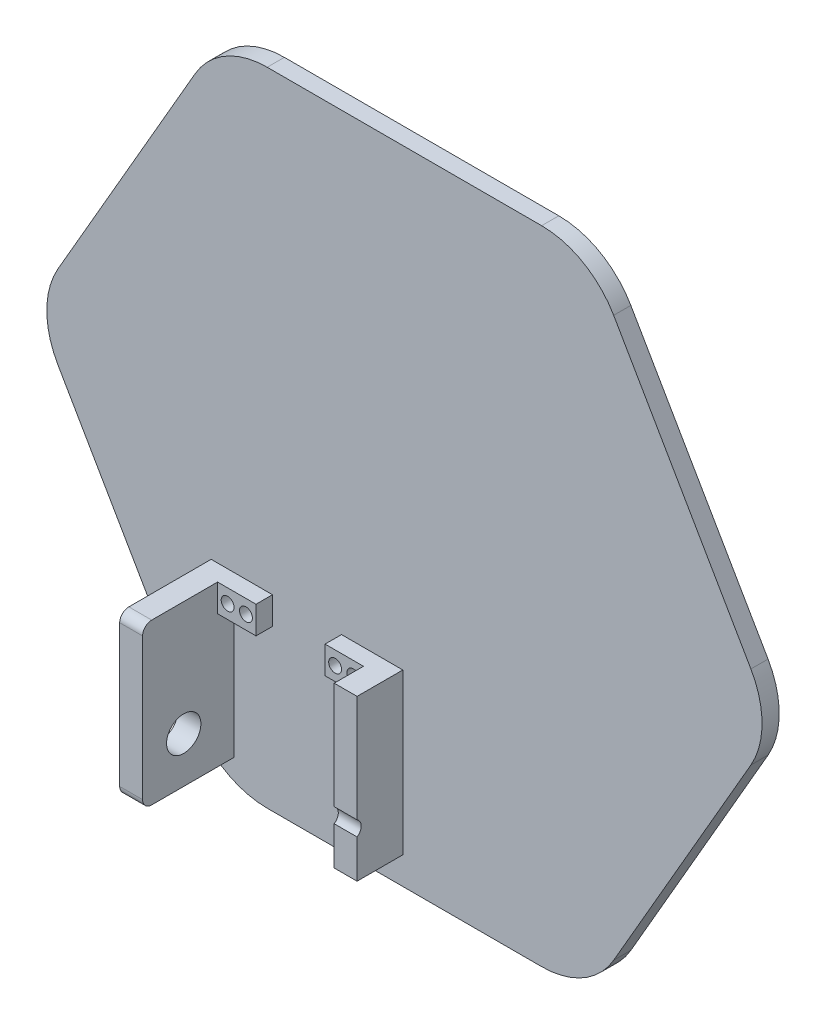
SolidWorks part; units mm, degrees
ref_plane "Front Plane" through (0, 0, 0) normal (0, 0, 1) x (1, 0, 0)
ref_plane "Top Plane" through (0, 0, 0) normal (0, 1, 0) x (1, 0, 0)
ref_plane "Right Plane" through (0, 0, 0) normal (1, 0, 0) x (0, 0, -1)
sketch "Sketch2" plane through (0, 0, 0) normal (0, 0, 1) x (1, 0, 0)
  line L1 (96.2019, 11.5481) -> (58.1019, 77.5392)
  line L2 (38.1, 89.0873) -> (-38.1, 89.0873)
  line L3 (-58.1019, 77.5392) -> (-96.2019, 11.5481)
  line L4 (-96.2019, -11.5481) -> (-58.1019, -77.5392)
  line L5 (-38.1, -89.0873) -> (38.1, -89.0873)
  line L6 (58.1019, -77.5392) -> (96.2019, -11.5481)
  circle A0 centre (0, 0) radius 89.0873 construction
  arc A1 (58.1019, 77.5392) -> (38.1, 89.0873) centre (38.1, 65.9911) ccw
  arc A2 (96.2019, 11.5481) -> (96.2019, -11.5481) centre (76.2, 0) cw
  arc A3 (38.1, -89.0873) -> (58.1019, -77.5392) centre (38.1, -65.9911) ccw
  arc A4 (-58.1019, -77.5392) -> (-38.1, -89.0873) centre (-38.1, -65.9911) ccw
  arc A5 (-96.2019, 11.5481) -> (-96.2019, -11.5481) centre (-76.2, 0) ccw
  arc A6 (-38.1, 89.0873) -> (-58.1019, 77.5392) centre (-38.1, 65.9911) ccw
  dimension "D1" = 76.2
extrude "Boss-Extrude1" add sketch "Sketch2" along normal blind 4.7625
sketch "Sketch4" plane through (0, 0, 4.7625) normal (0, 0, 1) x (1, 0, 0)
  line L0 (-38.1, -89.0873) -> (38.1, -89.0873) construction
  line L1 (-53.6569, -81.4673) -> (-47.3069, -81.4673)
  line L2 (-53.6569, -81.4673) -> (-53.6569, -37.0173)
  line L3 (-53.6569, -37.0173) -> (-47.3069, -37.0173)
  line L4 (-47.3069, -81.4673) -> (-47.3069, -37.0173)
  point P17 (0, 0)
  dimension "D1" = 6.35
  dimension "D2" = 44.45
  dimension "D3" = 7.62
  dimension "D4" = 4.445
extrude "Boss-Extrude3" add sketch "Sketch4" along normal blind 25.4
sketch "Sketch5" plane through (0, 0, 4.7625) normal (0, 0, 1) x (1, 0, 0)
  line L1 (-6.7975, -81.4673) -> (-0.4475, -81.4673)
  line L2 (-6.7975, -81.4673) -> (-6.7975, -37.0173)
  line L3 (-6.7975, -37.0173) -> (-0.4475, -37.0173)
  line L4 (-0.4475, -81.4673) -> (-0.4475, -37.0173)
  line L6 (-53.6569, -81.4673) -> (-47.3069, -81.4673) construction
  point P19 (0, 0)
  dimension "D1" = 6.35
extrude "Boss-Extrude6" add sketch "Sketch5" along normal blind 12.7
sketch "Sketch6" plane through (0, 0, 4.7625) normal (0, 0, 1) x (1, 0, 0)
  line L0 (-17.4655, -37.0173) -> (-6.7975, -37.0173)
  line L1 (-47.3069, -37.0173) -> (-36.6389, -37.0173)
  line L2 (-47.3069, -37.0173) -> (-47.3069, -44.6373)
  line L3 (-47.3069, -44.6373) -> (-36.6389, -44.6373)
  line L4 (-36.6389, -37.0173) -> (-36.6389, -44.6373)
  line L5 (-17.4655, -37.0173) -> (-17.4655, -44.6373)
  line L6 (-17.4655, -44.6373) -> (-6.7975, -44.6373)
  line L7 (-6.7975, -37.0173) -> (-6.7975, -44.6373)
  line L8 (-6.7975, -37.0173) -> (-6.7975, -81.4673) construction
  line L9 (-0.4475, -37.0173) -> (-6.7975, -37.0173) construction
  line L10 (-0.4475, -81.4673) -> (-0.4475, -37.0173) construction
  line L12 (-53.6569, -37.0173) -> (-53.6569, -81.4673) construction
  point P16 (0, 0)
  dimension "D1" = 7.62
  dimension "D2" = 17.018
  dimension "D3" = 7.62
  dimension "D4" = 17.018
extrude "Boss-Extrude5" add sketch "Sketch6" along normal blind 4.572
sketch "Sketch7" plane through (0, 0, 9.3345) normal (0, 0, 1) x (1, 0, 0)
  line L0 (-47.3069, -44.6373) -> (-36.6389, -44.6373) construction
  line L1 (-36.6389, -44.6373) -> (-36.6389, -37.0173) construction
  line L2 (-17.4655, -44.6373) -> (-6.7975, -44.6373) construction
  line L3 (-17.4655, -37.0173) -> (-17.4655, -44.6373) construction
  circle A0 centre (-44.5129, -40.8273) radius 1.7907
  circle A1 centre (-39.4329, -40.8273) radius 1.7907
  circle A2 centre (-14.6715, -40.8273) radius 1.7907
  circle A3 centre (-9.5915, -40.8273) radius 1.7907
  dimension "D1" = 3.5814
  dimension "D2" = 3.81
  dimension "D8" = 3.5814
  dimension "D9" = 3.5814
  dimension "D10" = 3.5814
  dimension "D3" = 5.08
  dimension "D4" = 2.794
  dimension "D5" = 3.81
  dimension "D6" = 2.794
  dimension "D7" = 5.08
extrude "Cut-Extrude1" cut sketch "Sketch7" against normal blind 6.731
sketch "Sketch9" plane through (-53.6569, 0, 0) normal (-1, 0, 0) x (0, 0, 1)
  line L0 (4.7625, -37.0173) -> (4.7625, -81.4673) construction
  line L1 (30.1625, -81.4673) -> (4.7625, -81.4673) construction
  circle A0 centre (7.5311, -68.7673) radius 2.286
  dimension "D1" = 4.572
  dimension "D2" = 2.7686
  dimension "D3" = 12.7
sketch "Sketch10" plane through (-53.6569, 0, 0) normal (-1, 0, 0) x (0, 0, 1)
  line L0 (30.1625, -81.4673) -> (4.7625, -81.4673) construction
  circle A0 centre (18.7325, -68.7673) radius 4.7625
  dimension "D1" = 9.525
  dimension "D2" = 11.2014
  dimension "D3" = 12.7
extrude "Cut-Extrude3" cut sketch "Sketch9" against normal blind 2.54
extrude "Cut-Extrude4" cut sketch "Sketch10" against normal up to surface (6.35 mm away) up to face at (-47.3069, -54.374, 14.7532)
fillet "Fillet2" radius 2.54 2 edges at (-50.4819, -37.0173, 30.1625) (-50.4819, -81.4673, 30.1625)
sketch3d "3DSketch1"
  line L0 (0, 0, 0) -> (0, 0, 50000) construction
sketch "Sketch11" plane through (-6.7975, 0, 0) normal (-1, 0, 0) x (0, 0, 1)
  circle A0 centre (18.7325, -68.7673) radius 4.7625 construction
  circle A1 centre (18.7325, -68.7673) radius 4.7625 construction
  circle A2 centre (18.7325, -68.7673) radius 2.413
  dimension "D1" = 4.826
extrude "Cut-Extrude5" cut sketch "Sketch11" against normal through all
